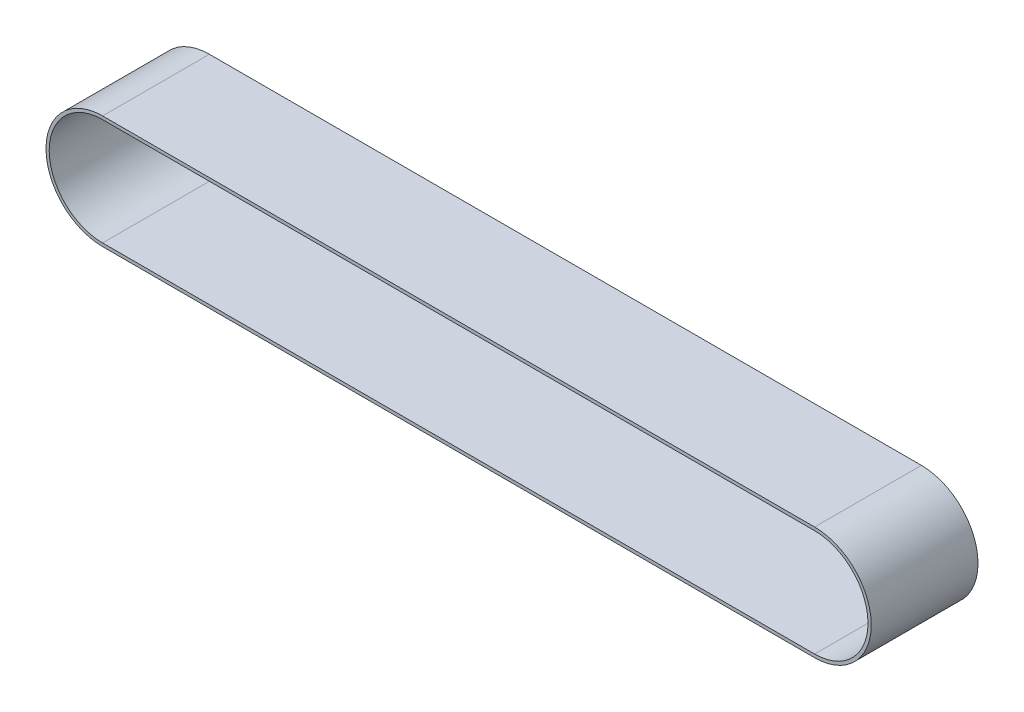
SolidWorks part; units mm, degrees
ref_plane "前视基准面" through (0, 0, 0) normal (0, 0, 1) x (1, 0, 0)
ref_plane "上视基准面" through (0, 0, 0) normal (0, 1, 0) x (1, 0, 0)
ref_plane "右视基准面" through (0, 0, 0) normal (1, 0, 0) x (0, 0, -1)
sketch "草图1" plane through (0, 0, 0) normal (0, 0, 1) x (1, 0, 0)
  line L0 (0, -15.9) -> (200, -15.9)
  line L1 (200, 15.9) -> (0, 15.9)
  line L2 (0, -15) -> (200, -15)
  line L3 (200, 15) -> (0, 15)
  arc A0 (0, 15.9) -> (0, -15.9) centre (0, 0) ccw
  arc A1 (200, -15.9) -> (200, 15.9) centre (200, 0) ccw
  arc A2 (0, 15) -> (0, -15) centre (0, 0) ccw
  arc A3 (200, -15) -> (200, 15) centre (200, 0) ccw
extrude "凸台-拉伸1" add sketch "草图1" along normal blind 30
ref_plane "基准面4" through (0, 0, 15) normal (0, 0, 1) x (1, 0, 0)
ref_plane "to_lane XY" through (0, 0, 15) normal (0, 0, 1) x (1, 0, 0)
ref_plane "to_lane XZ" through (0, 0, 0) normal (0, -1, 0) x (-1, 0, 0)
ref_plane "to_lane YZ" through (0, 0, 0) normal (1, 0, 0) x (0, 0, -1)
ref_axis "to_lane X" through (-80.9, 0, 15) along (1, 0, 0)
ref_axis "to_lane Y" through (0, -50, 15) along (0, 1, 0)
ref_axis "to_lane Z" through (0, 0, 80.9) along (0, 0, -1)
sketch3d "to_lane"
  point P0 (0, 0, 15)
